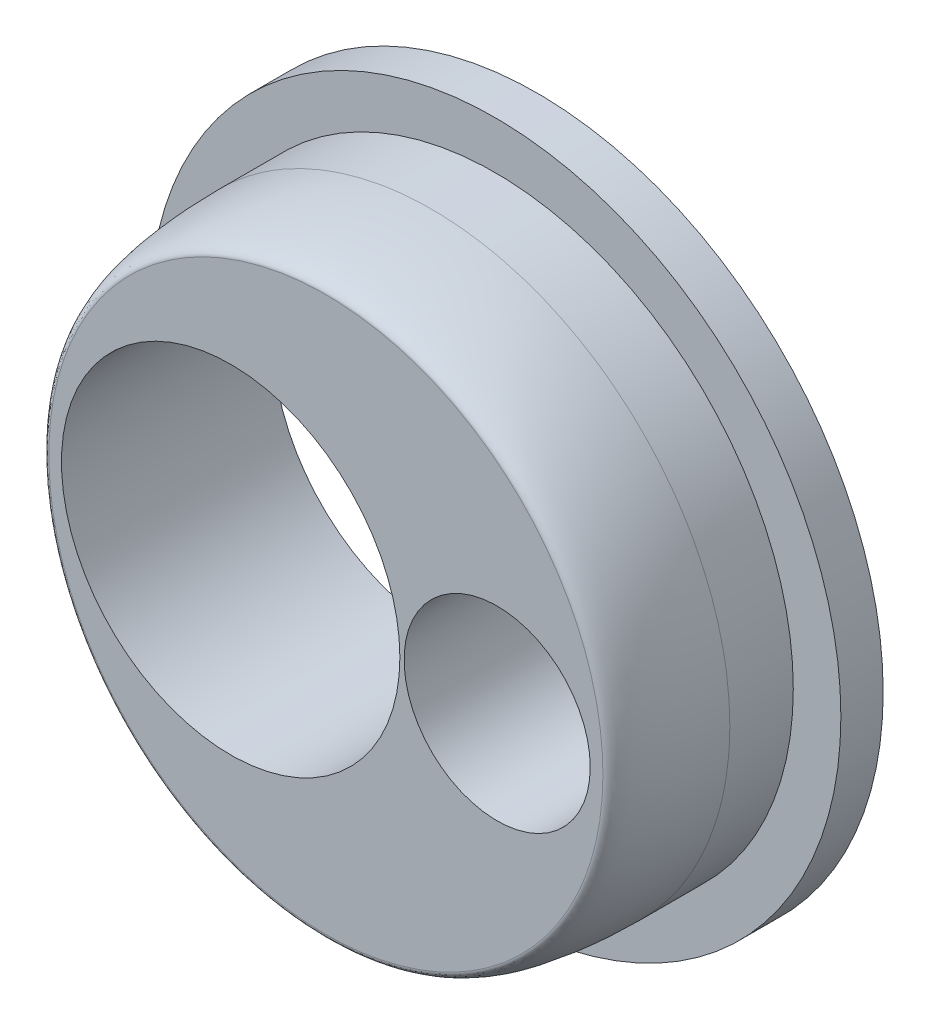
SolidWorks part; units mm, degrees
ref_plane "前视基准面" through (0, 0, 0) normal (0, 0, 1) x (1, 0, 0)
ref_plane "上视基准面" through (0, 0, 0) normal (0, 1, 0) x (1, 0, 0)
ref_plane "右视基准面" through (0, 0, 0) normal (1, 0, 0) x (0, 0, -1)
sketch "草图1" plane through (0, 0, 0) normal (0, 0, 1) x (1, 0, 0)
  circle A0 centre (0, 0) radius 16.35
  circle A1 centre (8.1, 0) radius 4.4
  circle A2 centre (-4.5, 0) radius 8
  circle A3 centre (0, 0) radius 12.5 construction
  dimension "D1" = 32.7
  dimension "D2" = 8.8
  dimension "D3" = 16
  dimension "D4" = 25
extrude "凸台-拉伸1" add sketch "草图1" along normal blind 2
sketch "草图2" plane through (0, 0, 2) normal (0, 0, 1) x (1, 0, 0)
  circle A0 centre (0, 0) radius 14.1
  circle A1 centre (8.1, 0) radius 4.4 construction
  circle A2 centre (-4.5, 0) radius 8 construction
  circle A3 centre (8.1, 0) radius 4.4
  circle A4 centre (-4.5, 0) radius 8
  dimension "D1" = 28.2
extrude "凸台-拉伸2" add sketch "草图2" along normal blind 8
fillet "圆角1" radius 5 1 edges at (14.1, 0, 10) second distance 1 first distance on face at (14.1, 0, 10)
